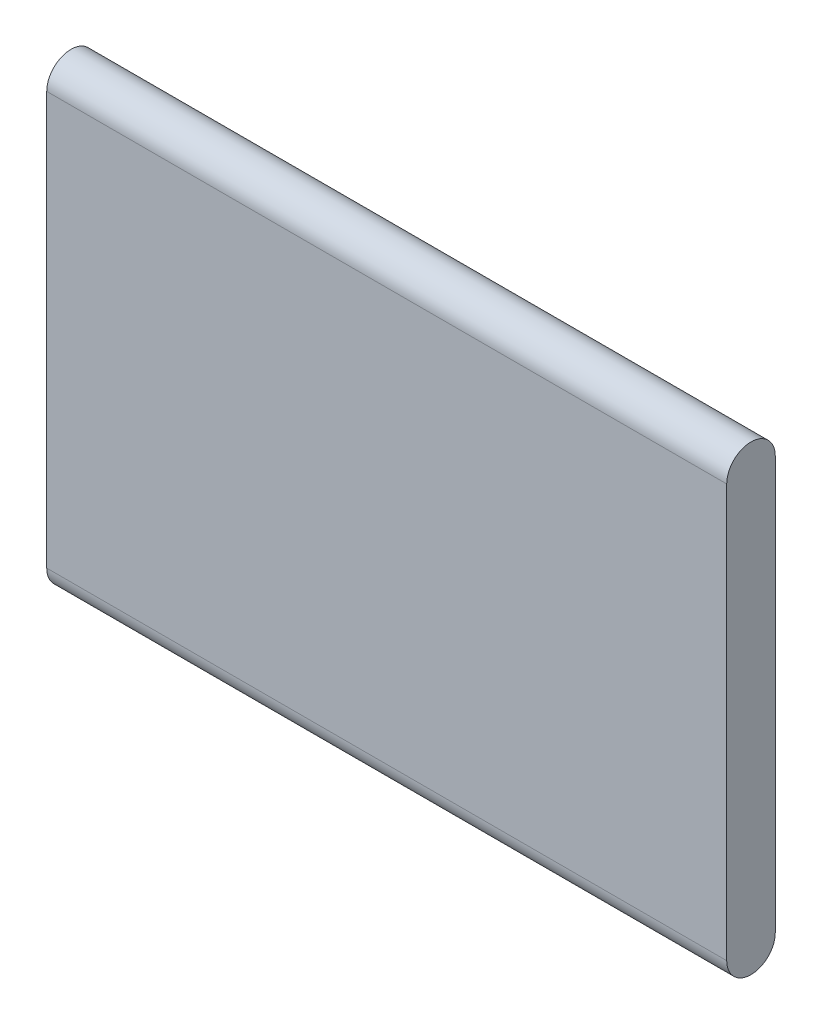
SolidWorks part; units mm, degrees
ref_plane "Front Plane" through (0, 0, 0) normal (0, 0, 1) x (1, 0, 0)
ref_plane "Top Plane" through (0, 0, 0) normal (0, 1, 0) x (1, 0, 0)
ref_plane "Right Plane" through (0, 0, 0) normal (1, 0, 0) x (0, 0, -1)
sketch "Sketch1" plane through (0, 0, 0) normal (1, 0, 0) x (0, 0, -1)
  line L0 (-25.4, 215.9) -> (25.4, -215.9) construction
  line L2 (-25.4, 215.9) -> (-25.4, -215.9)
  line L4 (25.4, 215.9) -> (25.4, -215.9)
  arc A0 (25.4, 215.9) -> (-25.4, 215.9) centre (0, 215.9) ccw
  arc A1 (-25.4, -215.9) -> (25.4, -215.9) centre (0, -215.9) ccw
  dimension "D1" = 25.4
  dimension "D2" = 482.6
extrude "Boss-Extrude1" add sketch "Sketch1" along normal mid plane 711.2
